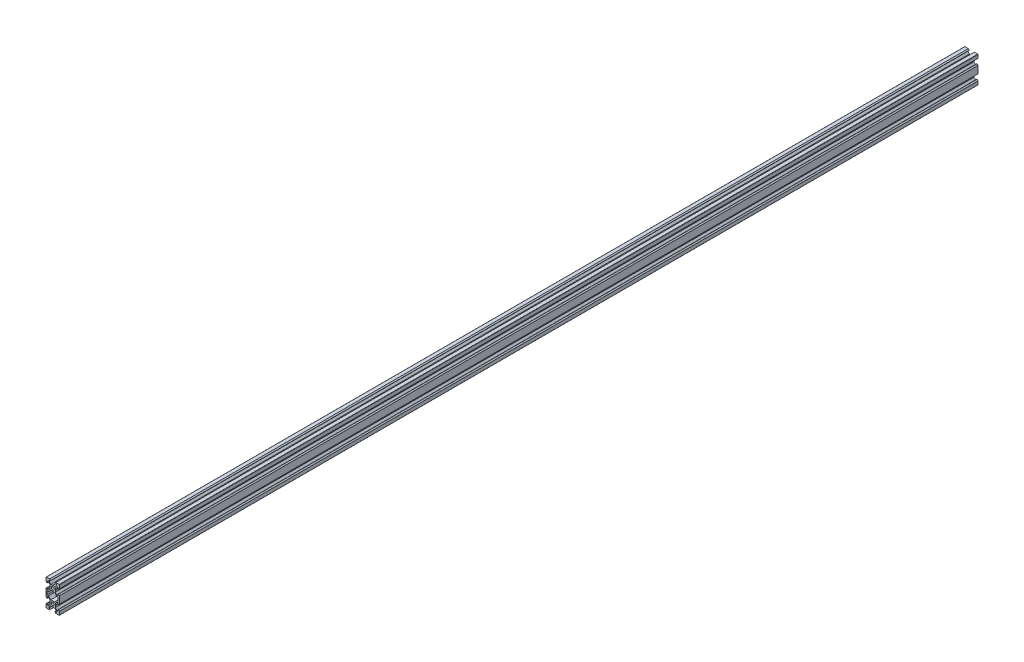
SolidWorks part; units mm, degrees
material "6061-T6 (SS)"
ref_plane "Front Plane" through (0, 0, 0) normal (0, 0, 1) x (1, 0, 0)
ref_plane "Top Plane" through (0, 0, 0) normal (0, 1, 0) x (1, 0, 0)
ref_plane "Right Plane" through (0, 0, 0) normal (1, 0, 0) x (0, 0, -1)
sketch "Sketch1" plane through (0, 0, 0) normal (0, 0, 1) x (1, 0, 0)
  line L0 (0, 0) -> (10, 0) construction
  line L1 (9.5, -20) -> (-9.5, -20)
  line L2 (10, -19.5) -> (10, 19.5)
  line L3 (9.5, 20) -> (-9.5, 20)
  line L4 (-10, -19.5) -> (-10, 19.5)
  line L5 (10, -20) -> (-10, 20) construction
  line L6 (10, 20) -> (-10, -20) construction
  circle A0 centre (0, 10) radius 2.1
  circle A1 centre (0, -10) radius 2.1
  arc A2 (-9.5, -20) -> (-10, -19.5) centre (-9.5, -19.5) cw
  arc A3 (9.5, -20) -> (10, -19.5) centre (9.5, -19.5) ccw
  arc A4 (10, 19.5) -> (9.5, 20) centre (9.5, 19.5) ccw
  arc A5 (-9.5, 20) -> (-10, 19.5) centre (-9.5, 19.5) ccw
  point P0 (0, 0)
  line B0 (0, 10) -> (0, 20) construction
  line B1 (0, 13.69) -> (-0.21, 13.9)
  line B2 (-0.21, 13.9) -> (-2.8393, 13.9)
  line B3 (-2.8393, 13.9) -> (-5.5, 16.5607)
  line B4 (-5.5, 16.5607) -> (-5.5, 18.2)
  line B5 (-5.5, 18.2) -> (-3.125, 18.2)
  line B6 (-3.125, 18.2) -> (-3.125, 18.545)
  line B7 (-3.125, 18.545) -> (-4.58, 20)
  line B8 (-4.58, 20) -> (4.58, 20)
  line B9 (0, 10) -> (-5.9132, 15.9132) construction
  line B10 (3.125, 18.545) -> (4.58, 20)
  line B11 (3.125, 18.2) -> (3.125, 18.545)
  line B12 (5.5, 18.2) -> (3.125, 18.2)
  line B13 (5.5, 16.5607) -> (5.5, 18.2)
  line B14 (2.8393, 13.9) -> (5.5, 16.5607)
  line B15 (0.21, 13.9) -> (2.8393, 13.9)
  line B16 (0, 13.69) -> (0.21, 13.9)
  line B17 (0, 10) -> (-10, 10) construction
  line B18 (-3.69, 10) -> (-3.9, 9.79)
  line B19 (-3.9, 9.79) -> (-3.9, 7.1607)
  line B20 (-3.9, 7.1607) -> (-6.5607, 4.5)
  line B21 (-6.5607, 4.5) -> (-8.2, 4.5)
  line B22 (-8.2, 4.5) -> (-8.2, 6.875)
  line B23 (-8.2, 6.875) -> (-8.545, 6.875)
  line B24 (-8.545, 6.875) -> (-10, 5.42)
  line B25 (-10, 5.42) -> (-10, 14.58)
  line B26 (0, 10) -> (-5.9132, 4.0868) construction
  line B27 (-8.545, 13.125) -> (-10, 14.58)
  line B28 (-8.2, 13.125) -> (-8.545, 13.125)
  line B29 (-8.2, 15.5) -> (-8.2, 13.125)
  line B30 (-6.5607, 15.5) -> (-8.2, 15.5)
  line B31 (-3.9, 12.8393) -> (-6.5607, 15.5)
  line B32 (-3.9, 10.21) -> (-3.9, 12.8393)
  line B33 (-3.69, 10) -> (-3.9, 10.21)
  line B34 (0, -10) -> (-10, -10) construction
  line B35 (-3.69, -10) -> (-3.9, -10.21)
  line B36 (-3.9, -10.21) -> (-3.9, -12.8393)
  line B37 (-3.9, -12.8393) -> (-6.5607, -15.5)
  line B38 (-6.5607, -15.5) -> (-8.2, -15.5)
  line B39 (-8.2, -15.5) -> (-8.2, -13.125)
  line B40 (-8.2, -13.125) -> (-8.545, -13.125)
  line B41 (-8.545, -13.125) -> (-10, -14.58)
  line B42 (-10, -14.58) -> (-10, -5.42)
  line B43 (0, -10) -> (-5.9132, -15.9132) construction
  line B44 (-8.545, -6.875) -> (-10, -5.42)
  line B45 (-8.2, -6.875) -> (-8.545, -6.875)
  line B46 (-8.2, -4.5) -> (-8.2, -6.875)
  line B47 (-6.5607, -4.5) -> (-8.2, -4.5)
  line B48 (-3.9, -7.1607) -> (-6.5607, -4.5)
  line B49 (-3.9, -9.79) -> (-3.9, -7.1607)
  line B50 (-3.69, -10) -> (-3.9, -9.79)
  line B51 (0, -10) -> (0, -20) construction
  line B52 (0, -13.69) -> (0.21, -13.9)
  line B53 (0.21, -13.9) -> (2.8393, -13.9)
  line B54 (2.8393, -13.9) -> (5.5, -16.5607)
  line B55 (5.5, -16.5607) -> (5.5, -18.2)
  line B56 (5.5, -18.2) -> (3.125, -18.2)
  line B57 (3.125, -18.2) -> (3.125, -18.545)
  line B58 (3.125, -18.545) -> (4.58, -20)
  line B59 (4.58, -20) -> (-4.58, -20)
  line B60 (0, -10) -> (5.9132, -15.9132) construction
  line B61 (-3.125, -18.545) -> (-4.58, -20)
  line B62 (-3.125, -18.2) -> (-3.125, -18.545)
  line B63 (-5.5, -18.2) -> (-3.125, -18.2)
  line B64 (-5.5, -16.5607) -> (-5.5, -18.2)
  line B65 (-2.8393, -13.9) -> (-5.5, -16.5607)
  line B66 (-0.21, -13.9) -> (-2.8393, -13.9)
  line B67 (0, -13.69) -> (-0.21, -13.9)
  line B68 (0, -10) -> (10, -10) construction
  line B69 (3.69, -10) -> (3.9, -9.79)
  line B70 (3.9, -9.79) -> (3.9, -7.1607)
  line B71 (3.9, -7.1607) -> (6.5607, -4.5)
  line B72 (6.5607, -4.5) -> (8.2, -4.5)
  line B73 (8.2, -4.5) -> (8.2, -6.875)
  line B74 (8.2, -6.875) -> (8.545, -6.875)
  line B75 (8.545, -6.875) -> (10, -5.42)
  line B76 (10, -5.42) -> (10, -14.58)
  line B77 (0, -10) -> (5.9132, -4.0868) construction
  line B78 (8.545, -13.125) -> (10, -14.58)
  line B79 (8.2, -13.125) -> (8.545, -13.125)
  line B80 (8.2, -15.5) -> (8.2, -13.125)
  line B81 (6.5607, -15.5) -> (8.2, -15.5)
  line B82 (3.9, -12.8393) -> (6.5607, -15.5)
  line B83 (3.9, -10.21) -> (3.9, -12.8393)
  line B84 (3.69, -10) -> (3.9, -10.21)
  line B85 (0, 10) -> (10, 10) construction
  line B86 (3.69, 10) -> (3.9, 10.21)
  line B87 (3.9, 10.21) -> (3.9, 12.8393)
  line B88 (3.9, 12.8393) -> (6.5607, 15.5)
  line B89 (6.5607, 15.5) -> (8.2, 15.5)
  line B90 (8.2, 15.5) -> (8.2, 13.125)
  line B91 (8.2, 13.125) -> (8.545, 13.125)
  line B92 (8.545, 13.125) -> (10, 14.58)
  line B93 (10, 14.58) -> (10, 5.42)
  line B94 (0, 10) -> (5.9132, 15.9132) construction
  line B95 (8.545, 6.875) -> (10, 5.42)
  line B96 (8.2, 6.875) -> (8.545, 6.875)
  line B97 (8.2, 4.5) -> (8.2, 6.875)
  line B98 (6.5607, 4.5) -> (8.2, 4.5)
  line B99 (3.9, 7.1607) -> (6.5607, 4.5)
  line B100 (3.9, 9.79) -> (3.9, 7.1607)
  line B101 (3.69, 10) -> (3.9, 9.79)
  line B102 (-8.2, -2.7) -> (-8.2, 2.7)
  line B103 (-8.2, 2.7) -> (-6.2393, 2.7)
  line B104 (-6.2393, 2.7) -> (-2.8393, 6.1)
  line B105 (-2.8393, 6.1) -> (2.8393, 6.1)
  line B106 (0, 6.1) -> (0, 0) construction
  line B107 (0, 0) -> (-8.2, 0) construction
  line B108 (6.2393, 2.7) -> (2.8393, 6.1)
  line B109 (8.2, 2.7) -> (6.2393, 2.7)
  line B110 (8.2, -2.7) -> (8.2, 2.7)
  line B111 (8.2, -2.7) -> (6.2393, -2.7)
  line B112 (6.2393, -2.7) -> (2.8393, -6.1)
  line B113 (-2.8393, -6.1) -> (2.8393, -6.1)
  line B114 (-6.2393, -2.7) -> (-2.8393, -6.1)
  line B115 (-8.2, -2.7) -> (-6.2393, -2.7)
  line B116 (0, 6.1) -> (0, 10) construction
  line B117 (0, 10) -> (-5.0927, 4.9073) construction
  dimension "D4" = 4.2
  dimension "D5" = 0.5
  dimension "D1" = 20
  dimension "D2" = 40
  dimension "D3" = 20
sketch_block_instance "V Slot 1-4"
sketch_block "V Slot 1" parameters "D1"=10, "D2"=11, "D3"=4.3, "D4"=1.8, "D5"=0.21, "D6"=45, "D7"=9.16, "D8"=1.5, "D9"=6.25
sketch_block_instance "V Slot 1-5"
sketch_block_instance "V Slot 1-6"
sketch_block_instance "V Slot 1-7"
sketch_block_instance "V Slot 1-8"
sketch_block_instance "V Slot 1-9"
sketch_block_instance "Center Cutout 1-1"
sketch_block "Center Cutout 1" parameters "D1"=5.4, "D2"=12.2, "D3"=8.2, "D4"=45, "D5"=10, "D6"=1.5
extrude "Boss-Extrude1" add sketch "Sketch1" along normal blind 1371.6 contours B101 B86 B87 B88 B89 B90 B91 B92 L2 A4 L3 B10 B11 B12 B13 B14 B15 B16 B1 B2 B3 B4 B5 B6 B7 A5 L4 B27 B28 B29 B30 B31 B32 B33 B18 B19 B20 B21 B22 B23 B24 B44 B45 B46 B47 B48 B49 B50 B35 region at (7.04, -19.5528, 0)
